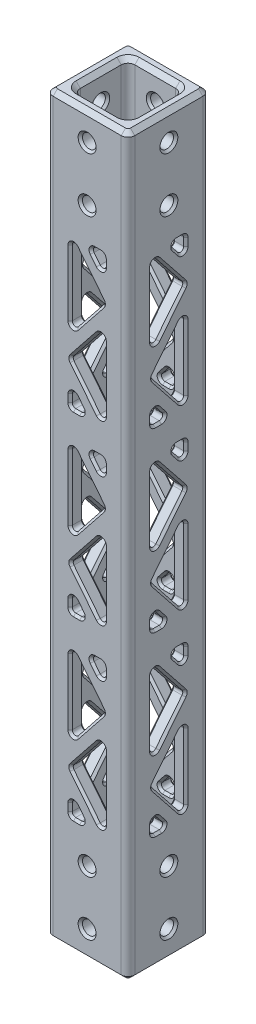
SolidWorks part; units mm, degrees
note: '?' marks a value the reader was unsure of.
ref_plane "Front Plane" through (0, 0, 0) normal (0, 0, 1) x (1, 0, 0)
ref_plane "Top Plane" through (0, 0, 0) normal (0, 1, 0) x (1, 0, 0)
ref_plane "Right Plane" through (0, 0, 0) normal (1, 0, 0) x (0, 0, -1)
sketch "Sketch1" plane through (0, 0, 0) normal (0, 1, 0) x (1, 0, 0)
  line L1 (-9.525, -9.525) -> (9.525, -9.525)
  line L2 (-9.525, -9.525) -> (-9.525, 9.525)
  line L3 (-9.525, 9.525) -> (9.525, 9.525)
  line L4 (9.525, -9.525) -> (9.525, 9.525)
  line L5 (-9.525, -9.525) -> (9.525, 9.525) construction
  line L6 (-9.525, 9.525) -> (9.525, -9.525) construction
  line L7 (-6.35, -6.35) -> (6.35, -6.35)
  line L8 (-6.35, -6.35) -> (-6.35, 6.35)
  line L9 (-6.35, 6.35) -> (6.35, 6.35)
  line L10 (6.35, -6.35) -> (6.35, 6.35)
  line L11 (-6.35, -6.35) -> (6.35, 6.35) construction
  line L12 (-6.35, 6.35) -> (6.35, -6.35) construction
  point P0 (0, 0)
  point P6 (0, 0)
  dimension "D1" = 19.05
  dimension "D2" = 19.05
  dimension "D3" = 12.7
extrude "Boss-Extrude1" add sketch "Sketch1" along normal mid plane 171.45 contours L3 L4 L1 L2
hole_wizard "1/8 (0.125) Diameter Hole1" positions "Sketch8" profile "Sketch9" hole size "1/8" standard "ANSI Inch" end condition through all
sketch "Sketch8" plane through (-9.525, 0, 0) normal (-1, 0, 0) x (0, 0, 1)
  line L4 (-9.525, 85.725) -> (9.525, 85.725) construction
  line L5 (0, 79.375) -> (0, 85.725) construction
  point P0 (0, 79.375)
  point P2 (0, 66.675)
  dimension "D1" = 12.7
  dimension "D2" = 6.35
sketch "Sketch9" plane through (-9.525, 79.375, 0) normal (0, 1, 0) x (0, 0, 1)
  line L0 (0, 0) -> (0, 19.05)
  line L1 (0, 19.05) -> (1.5875, 19.05)
  line L2 (1.5875, 19.05) -> (1.5875, 0)
  line L5 (1.5875, 0) -> (0, 0)
  line L11 (0, -6.35) -> (0, 107.95) construction
  dimension "Thru Hole Dia." = 3.175
  dimension "Thru Hole Depth" = 19.05
hole_wizard "1/8 (0.125) Diameter Hole2" positions "Sketch10" profile "Sketch11" hole size "1/8" standard "ANSI Inch" end condition through all
sketch "Sketch10" plane through (-9.525, 0, 0) normal (-1, 0, 0) x (0, 0, 1)
  line L0 (0, -85.725) -> (0, -79.375) construction
  line L1 (-9.525, -85.725) -> (9.525, -85.725) construction
  point P0 (0, -66.675)
  point P2 (0, -79.375)
  dimension "D1" = 12.7
  dimension "D2" = 6.35
sketch "Sketch11" plane through (-9.525, -66.675, 0) normal (0, 1, 0) x (0, 0, 1)
  line L0 (0, 0) -> (0, 19.05)
  line L1 (0, 19.05) -> (1.5875, 19.05)
  line L2 (1.5875, 19.05) -> (1.5875, 0)
  line L5 (1.5875, 0) -> (0, 0)
  line L11 (0, -6.35) -> (0, 107.95) construction
  dimension "Thru Hole Dia." = 3.175
  dimension "Thru Hole Depth" = 19.05
hole_wizard "1/8 (0.125) Diameter Hole3" positions "Sketch15" profile "Sketch16" hole size "1/8" standard "ANSI Inch" end condition through all
sketch "Sketch15" plane through (0, 0, 9.525) normal (0, 0, 1) x (1, 0, 0)
  line L0 (0, -85.725) -> (0, -79.375) construction
  line L1 (-9.525, -85.725) -> (9.525, -85.725) construction
  line L2 (0, -79.375) -> (0, -66.675) construction
  line L4 (0, 66.675) -> (0, 79.375) construction
  line L5 (0, 79.375) -> (0, 85.725) construction
  line L6 (-9.525, 85.725) -> (9.525, 85.725) construction
  point P0 (0, 79.375)
  point P2 (0, 66.675)
  point P4 (0, -66.675)
  point P6 (0, -79.375)
  dimension "D1" = 6.35
  dimension "D2" = 12.7
sketch "Sketch16" plane through (0, 79.375, 9.525) normal (1, 0, 0) x (0, -1, 0)
  line L0 (0, 0) -> (0, 19.05)
  line L1 (0, 19.05) -> (1.5875, 19.05)
  line L2 (1.5875, 19.05) -> (1.5875, 0)
  line L5 (1.5875, 0) -> (0, 0)
  line L11 (0, -6.35) -> (0, 107.95) construction
  dimension "Thru Hole Dia." = 3.175
  dimension "Thru Hole Depth" = 19.05
sketch "Sketch14" plane through (0, 0, 0) normal (1, 0, 0) x (0, 0, -1)
  line L0 (-3.9688, 58.7375) -> (3.9688, 58.7375) construction
  line L3 (3.9688, 58.7375) -> (3.9688, -58.7375) construction
  line L6 (3.9688, -58.7375) -> (-3.9688, -58.7375) construction
  line L9 (-3.9688, -58.7375) -> (-3.9688, 58.7375) construction
  line L10 (0, 58.7375) -> (0, 65.0875) construction
  line L11 (0, -65.0875) -> (0, -58.7375) construction
  line L12 (-3.9688, 23.8125) -> (3.9688, 23.8125) construction
  line L13 (-3.9688, 17.4625) -> (3.9688, 17.4625) construction
  line L14 (-3.9688, -17.4625) -> (3.9688, -17.4625) construction
  line L15 (-3.9688, -23.8125) -> (3.9688, -23.8125) construction
  line L16 (0, -58.7375) -> (0, -23.8125) construction
  line L17 (0, -23.8125) -> (0, -17.4625) construction
  line L18 (0, -17.4625) -> (0, 17.4625) construction
  line L19 (0, 17.4625) -> (0, 23.8125) construction
  line L20 (0, 23.8125) -> (0, 58.7375) construction
  line L21 (-3.9688, 58.7375) -> (-0.0935, 58.7375)
  line L22 (-0.0935, 58.7375) -> (-3.9688, 53.8821)
  line L23 (-3.9688, 53.8821) -> (-3.9688, 58.7375)
  line L24 (3.9688, 58.7375) -> (-3.9688, 48.7924)
  line L25 (-3.9688, 48.7924) -> (3.9688, 38.8473)
  line L26 (3.9688, 38.8473) -> (3.9688, 58.7375)
  line L27 (-3.9688, 23.8125) -> (3.9688, 33.7576)
  line L28 (3.9688, 33.7576) -> (-3.9688, 43.7027)
  line L29 (-3.9688, 43.7027) -> (-3.9688, 23.8125)
  line L30 (0, 53.765) -> (-2.4815, 55.7455) construction
  line L31 (0, 43.8199) -> (-2.4815, 41.8393) construction
  line L32 (0.0935, 23.8125) -> (3.9688, 23.8125)
  line L33 (3.9688, 23.8125) -> (3.9688, 28.6679)
  line L34 (3.9688, 28.6679) -> (0.0935, 23.8125)
  line L35 (0, 28.785) -> (2.4815, 26.8045) construction
  line L36 (-3.9688, 17.4625) -> (-0.0935, 17.4625)
  line L37 (-0.0935, 17.4625) -> (-3.9688, 12.6071)
  line L38 (-3.9688, 12.6071) -> (-3.9688, 17.4625)
  line L39 (3.9688, 17.4625) -> (-3.9688, 7.5174)
  line L40 (-3.9688, 7.5174) -> (3.9688, -2.4277)
  line L41 (3.9688, -2.4277) -> (3.9688, 17.4625)
  line L42 (0, 12.49) -> (-2.4815, 14.4705) construction
  line L43 (-3.9688, -17.4625) -> (3.9688, -7.5174)
  line L44 (3.9688, -7.5174) -> (-3.9688, 2.4277)
  line L45 (-3.9688, 2.4277) -> (-3.9688, -17.4625)
  line L46 (0, -2.5449) -> (2.4815, -0.5643) construction
  line L47 (0.0935, -17.4625) -> (3.9688, -17.4625)
  line L48 (3.9688, -17.4625) -> (3.9688, -12.6071)
  line L49 (3.9688, -12.6071) -> (0.0935, -17.4625)
  line L50 (2.0311, -15.0348) -> (-0.4504, -13.0542) construction
  line L51 (-3.9688, -23.8125) -> (-0.0935, -23.8125)
  line L52 (-0.0935, -23.8125) -> (-3.9688, -28.6679)
  line L53 (-3.9688, -28.6679) -> (-3.9688, -23.8125)
  line L54 (3.9688, -23.8125) -> (-3.9688, -33.7576)
  line L55 (-3.9688, -33.7576) -> (3.9688, -43.7027)
  line L56 (3.9688, -43.7027) -> (3.9688, -23.8125)
  line L57 (3.9688, -58.7375) -> (0.0935, -58.7375)
  line L58 (0.0935, -58.7375) -> (3.9688, -53.8821)
  line L59 (3.9688, -53.8821) -> (3.9688, -58.7375)
  line L60 (-3.9688, -58.7375) -> (3.9688, -48.7924)
  line L61 (3.9688, -48.7924) -> (-3.9688, -38.8473)
  line L62 (-3.9688, -38.8473) -> (-3.9688, -58.7375)
  line L63 (0, -28.785) -> (-2.4815, -26.8045) construction
  line L64 (0, -38.7301) -> (-2.4815, -40.7107) construction
  line L65 (2.0311, -56.3098) -> (-0.4504, -54.3292) construction
  circle A8 centre (0, 66.675) radius 1.5875 construction
  circle A9 centre (0, -66.675) radius 1.5875 construction
  dimension "D3" = 3.175
  dimension "D2" = 6.35
  dimension "D1" = 7.9375
extrude "Cut-Extrude1" cut sketch "Sketch14" against normal up to next
ref_axis "Axis1" through (0, -87.3125, 0) along (0, 1, 0)?
pattern_circular "CirPattern1" count 4 over 360 about axis through (0, 0, 0) along (0, 1, 0) of "Cut-Extrude1"
fillet "Fillet1" radius 1.5875 8 edges at (9.525, 0, -9.525) (9.525, 0, 9.525) (-9.525, 0, -9.525) (-9.525, 0, 9.525) (6.35, 0, -6.35) (6.35, 0, 6.35) (-6.35, 0, 6.35) (-6.35, 0, -6.35)
fillet "Fillet2" radius 0.7937 71 edges at (-3.9688, -33.7576, -7.9375) (-3.9688, -28.6679, -7.9375) (-0.0935, -23.8125, -7.9375) (-3.9688, -23.8125, -7.9375) (-3.9688, -17.4625, -7.9375) (3.9687, -7.5174, -7.9375) (-3.9688, 2.4277, -7.9375) (-3.9688, 12.6071, -7.9375) (-3.9688, -58.7375, -7.9375) (3.9687, -12.6071, -7.9375) (3.9687, -53.8821, -7.9375) (0.0935, -58.7375, -7.9375) (3.9687, 58.7375, -7.9375) (-3.9688, 53.8821, -7.9375) (-0.0935, 58.7375, -7.9375) (-3.9688, 58.7375, -7.9375) (7.9375, -43.7027, 3.9688) (7.9375, -28.6679, -3.9688) (7.9375, -23.8125, -0.0935) (7.9375, -17.4625, -3.9687) (7.9375, -7.5174, 3.9687) (7.9375, 2.4277, -3.9688) (7.9375, 17.4625, 3.9688) (7.9375, 23.8125, 0.0935) (7.9375, 33.7576, 3.9688) (7.9375, 43.7027, -3.9688) (7.9375, 17.4625, -0.0935) (7.9375, 17.4625, -3.9688) (7.9375, -58.7375, -3.9687) (7.9375, -48.7924, 3.9688) (7.9375, -17.4625, 0.0935) (7.9375, -17.4625, 3.9688) (7.9375, -12.6071, 3.9688) (7.9375, 58.7375, 3.9688) (7.9375, 48.7924, -3.9687) (3.9688, -28.6679, 7.9375) (-3.9687, 28.6679, 7.9375) (-0.0935, 23.8125, 7.9375) (3.9688, 23.8125, 7.9375) (3.9688, 43.7027, 7.9375) (3.9688, 12.6071, 7.9375) (0.0935, 17.4625, 7.9375) (3.9688, 17.4625, 7.9375) (3.9688, -38.8473, 7.9375) (-0.0935, -17.4625, 7.9375) (-3.9687, -17.4625, 7.9375) (-3.9687, 58.7375, 7.9375) (3.9688, 48.7924, 7.9375) (0.0935, 58.7375, 7.9375) (3.9688, 58.7375, 7.9375) (7.9375, 58.7375, -3.9688) (-7.9375, -58.7375, -0.0935) (-7.9375, -58.7375, -3.9688) (-7.9375, -48.7924, -3.9687) (-7.9375, -58.7375, 3.9687) (-7.9375, -43.7027, -3.9688) (-7.9375, -28.6679, 3.9688) (-7.9375, -17.4625, -3.9688) (-7.9375, -17.4625, 3.9687) (-7.9375, 2.4277, 3.9688) (-7.9375, -7.5174, -3.9687) (-7.9375, -2.4277, -3.9688) (-7.9375, 12.6071, 3.9687) (-7.9375, 17.4625, 3.9688) (-7.9375, 28.6679, -3.9688) (-7.9375, 43.7027, 3.9688) (-7.9375, 48.7924, 3.9688) (-7.9375, 38.8473, -3.9688) (-7.9375, 58.7375, -3.9688) (-7.9375, 58.7375, 0.0935) (-7.9375, 58.7375, 3.9688)
chamfer "Chamfer2" distance 1.016 angle 45 32 edges at (5.885, 85.725, -5.885) (0, 85.725, -6.35) (-5.885, 85.725, -5.885) (-6.35, 85.725, 0) (-5.885, 85.725, 5.885) (0, 85.725, 6.35) (5.885, 85.725, 5.885) (6.35, 85.725, 0) (9.06, 85.725, 9.06) (0, 85.725, 9.525) (-9.06, 85.725, 9.06) (-9.525, 85.725, 0) (-9.06, 85.725, -9.06) (0, 85.725, -9.525) (9.06, 85.725, -9.06) (9.525, 85.725, 0) (-5.885, -85.725, -5.885) (0, -85.725, -6.35) (5.885, -85.725, -5.885) (6.35, -85.725, 0) (5.885, -85.725, 5.885) (0, -85.725, 6.35) (-5.885, -85.725, 5.885) (-6.35, -85.725, 0) (-9.06, -85.725, -9.06) (-9.525, -85.725, 0) (-9.06, -85.725, 9.06) (0, -85.725, 9.525) (9.06, -85.725, 9.06) (9.525, -85.725, 0) (9.06, -85.725, -9.06) (0, -85.725, -9.525)
chamfer "Chamfer1" distance 0.508 angle 45 608 edges at (-3.4373, 25.3303, -6.35) (-3.4373, 25.3303, -9.525) (3.7469, 33.7576, -6.35) (3.7469, 33.7576, -9.525) (-3.4373, 42.1849, -6.35) (-3.4373, 42.1849, -9.525) (-3.4373, 14.1249, -6.35) (-3.4373, 14.1249, -9.525) (-1.0274, 17.013, -6.35) (-1.0274, 17.013, -9.525) (-3.7363, 17.23, -6.35) (-3.7363, 17.23, -9.525) (-3.4373, -57.2197, -6.35) (-3.4373, -57.2197, -9.525) (3.7469, -48.7924, -6.35) (3.7469, -48.7924, -9.525) (-3.4373, -40.3651, -6.35) (-3.4373, -40.3651, -9.525) (1.0274, -17.013, -6.35) (1.0274, -17.013, -9.525) (3.7363, -17.23, -6.35) (3.7363, -17.23, -9.525) (3.4373, -14.1249, -6.35) (3.4373, -14.1249, -9.525) (3.4373, -55.3999, -6.35) (3.4373, -55.3999, -9.525) (1.0274, -58.288, -6.35) (1.0274, -58.288, -9.525) (3.7363, -58.505, -6.35) (3.7363, -58.505, -9.525) (3.4373, 57.2197, -6.35) (3.4373, 57.2197, -9.525) (-3.7469, 48.7924, -6.35) (-3.7469, 48.7924, -9.525) (3.4373, 40.3651, -6.35) (3.4373, 40.3651, -9.525) (-3.4373, 55.3999, -6.35) (-3.4373, 55.3999, -9.525) (-1.0274, 58.288, -6.35) (-1.0274, 58.288, -9.525) (-3.7363, 58.505, -6.35) (-3.7363, 58.505, -9.525) (6.35, -25.3303, 3.4373) (9.525, -25.3303, 3.4373) (6.35, -33.7576, -3.7469) (9.525, -33.7576, -3.7469) (6.35, -42.1849, 3.4373) (9.525, -42.1849, 3.4373) (6.35, -27.1501, -3.4373) (9.525, -27.1501, -3.4373) (6.35, -24.262, -1.0274) (9.525, -24.262, -1.0274) (6.35, -24.045, -3.7363) (9.525, -24.045, -3.7363) (6.35, -15.9447, -3.4373) (9.525, -15.9447, -3.4373) (6.35, -7.5174, 3.7469) (9.525, -7.5174, 3.7469) (6.35, 0.9099, -3.4373) (9.525, 0.9099, -3.4373) (6.35, 15.9447, 3.4373) (9.525, 15.9447, 3.4373) (6.35, 7.5174, -3.7469) (9.525, 7.5174, -3.7469) (6.35, -0.9099, 3.4373) (9.525, -0.9099, 3.4373) (6.35, 27.1501, 3.4373) (9.525, 27.1501, 3.4373) (6.35, 24.262, 1.0274) (9.525, 24.262, 1.0274) (6.35, 24.045, 3.7363) (9.525, 24.045, 3.7363) (6.35, 25.3303, -3.4373) (9.525, 25.3303, -3.4373) (6.35, 33.7576, 3.7469) (9.525, 33.7576, 3.7469) (6.35, 42.1849, -3.4373) (9.525, 42.1849, -3.4373) (6.35, 14.1249, -3.4373) (9.525, 14.1249, -3.4373) (6.35, 17.013, -1.0274) (9.525, 17.013, -1.0274) (6.35, 17.23, -3.7363) (9.525, 17.23, -3.7363) (6.35, -57.2197, -3.4373) (9.525, -57.2197, -3.4373) (6.35, -48.7924, 3.7469) (9.525, -48.7924, 3.7469) (6.35, -40.3651, -3.4373) (9.525, -40.3651, -3.4373) (6.35, -17.013, 1.0274) (9.525, -17.013, 1.0274) (6.35, -17.23, 3.7363) (9.525, -17.23, 3.7363) (6.35, -14.1249, 3.4373) (9.525, -14.1249, 3.4373) (6.35, -55.3999, 3.4373) (9.525, -55.3999, 3.4373) (6.35, -58.288, 1.0274) (9.525, -58.288, 1.0274) (6.35, -58.505, 3.7363) (9.525, -58.505, 3.7363) (6.35, 57.2197, 3.4373) (9.525, 57.2197, 3.4373) (6.35, 48.7924, -3.7469) (9.525, 48.7924, -3.7469) (6.35, 40.3651, 3.4373) (9.525, 40.3651, 3.4373) (6.35, 55.3999, -3.4373) (9.525, 55.3999, -3.4373) (6.35, 58.288, -1.0274) (9.525, 58.288, -1.0274) (-3.4373, -25.3303, 6.35) (-3.4373, -25.3303, 9.525) (3.7469, -33.7576, 6.35) (3.7469, -33.7576, 9.525) (-3.4373, -42.1849, 6.35) (-3.4373, -42.1849, 9.525) (3.4373, -27.1501, 6.35) (3.4373, -27.1501, 9.525) (1.0274, -24.262, 6.35) (1.0274, -24.262, 9.525) (3.7363, -24.045, 6.35) (3.7363, -24.045, 9.525) (3.4373, -15.9447, 6.35) (3.4373, -15.9447, 9.525) (-3.7469, -7.5174, 6.35) (-3.7469, -7.5174, 9.525) (3.4373, 0.9099, 6.35) (3.4373, 0.9099, 9.525) (-3.4373, 15.9447, 6.35) (-3.4373, 15.9447, 9.525) (3.7469, 7.5174, 6.35) (3.7469, 7.5174, 9.525) (-3.4373, -0.9099, 6.35) (-3.4373, -0.9099, 9.525) (-3.4373, 27.1501, 6.35) (-3.4373, 27.1501, 9.525) (-1.0274, 24.262, 6.35) (-1.0274, 24.262, 9.525) (-3.7363, 24.045, 6.35) (-3.7363, 24.045, 9.525) (3.4373, 25.3303, 6.35) (3.4373, 25.3303, 9.525) (-3.7469, 33.7576, 6.35) (-3.7469, 33.7576, 9.525) (3.4373, 42.1849, 6.35) (3.4373, 42.1849, 9.525) (3.4373, 14.1249, 6.35) (3.4373, 14.1249, 9.525) (1.0274, 17.013, 6.35) (1.0274, 17.013, 9.525) (3.7363, 17.23, 6.35) (3.7363, 17.23, 9.525) (3.4373, -57.2197, 6.35) (3.4373, -57.2197, 9.525) (-3.7469, -48.7924, 6.35) (-3.7469, -48.7924, 9.525) (3.4373, -40.3651, 6.35) (3.4373, -40.3651, 9.525) (-1.0274, -17.013, 6.35) (-1.0274, -17.013, 9.525) (-3.7363, -17.23, 6.35) (-3.7363, -17.23, 9.525) (-3.4373, -14.1249, 6.35) (-3.4373, -14.1249, 9.525) (-3.4373, -55.3999, 6.35) (-3.4373, -55.3999, 9.525) (-1.0274, -58.288, 6.35) (-1.0274, -58.288, 9.525) (-3.7363, -58.505, 6.35) (-3.7363, -58.505, 9.525) (-3.4373, 57.2197, 6.35) (-3.4373, 57.2197, 9.525) (3.7469, 48.7924, 6.35) (3.7469, 48.7924, 9.525) (-3.4373, 40.3651, 6.35) (-3.4373, 40.3651, 9.525) (3.4373, 55.3999, 6.35) (3.4373, 55.3999, 9.525) (1.0274, 58.288, 6.35) (1.0274, 58.288, 9.525) (3.7363, 58.505, 6.35) (3.7363, 58.505, 9.525) (6.35, 58.505, -3.7363) (9.525, 58.505, -3.7363) (6.35, 66.675, 1.5875) (-6.35, 66.675, -1.5875) (-9.525, 66.675, 1.5875) (9.525, 66.675, 1.5875) (6.35, 79.375, 1.5875) (-6.35, 79.375, -1.5875) (-9.525, 79.375, 1.5875) (9.525, 79.375, 1.5875) (6.35, -79.375, 1.5875) (-6.35, -79.375, -1.5875) (-9.525, -79.375, 1.5875) (9.525, -79.375, 1.5875) (6.35, -66.675, 1.5875) (-6.35, -66.675, -1.5875) (-9.525, -66.675, 1.5875) (9.525, -66.675, 1.5875) (-9.525, -58.7375, -2.4588) (-6.35, -58.7375, -2.4588) (-9.525, -56.5513, -1.8384) (-6.35, -56.5513, -1.8384) (-9.525, -57.0464, -3.9688) (-6.35, -57.0464, -3.9688) (-9.525, -44.4582, -0.5095) (-6.35, -44.4582, -0.5095) (-9.525, -53.1266, -0.5095) (-6.35, -53.1266, -0.5095) (-9.525, -48.7924, 3.9688) (-6.35, -48.7924, 3.9688) (-9.525, -38.0918, 0.5095) (-6.35, -38.0918, 0.5095) (-9.525, -29.4234, 0.5095) (-6.35, -29.4234, 0.5095) (-9.525, -33.7576, -3.9688) (-6.35, -33.7576, -3.9688) (-9.525, -25.9987, 1.8384) (-6.35, -25.9987, 1.8384) (-9.525, -25.5036, 3.9688) (-6.35, -25.5036, 3.9688) (-9.525, -23.8125, 2.4588) (-6.35, -23.8125, 2.4588) (-9.525, -15.7714, -3.9688) (-6.35, -15.7714, -3.9688) (-9.525, -17.4625, -2.4588) (-6.35, -17.4625, -2.4588) (-9.525, -15.2763, -1.8384) (-6.35, -15.2763, -1.8384) (-9.525, -11.8516, -0.5095) (-6.35, -11.8516, -0.5095) (-9.525, -7.5174, 3.9688) (-6.35, -7.5174, 3.9688) (-9.525, -3.1832, -0.5095) (-6.35, -3.1832, -0.5095) (-9.525, 3.1832, 0.5095) (-6.35, 3.1832, 0.5095) (-9.525, 11.8516, 0.5095) (-6.35, 11.8516, 0.5095) (-9.525, 7.5174, -3.9688) (-6.35, 7.5174, -3.9688) (-9.525, 17.4625, 2.4588) (-6.35, 17.4625, 2.4588) (-9.525, 15.2763, 1.8384) (-6.35, 15.2763, 1.8384) (-9.525, 15.7714, 3.9688) (-6.35, 15.7714, 3.9688) (-9.525, 23.8125, -2.4588) (-6.35, 23.8125, -2.4588) (-9.525, 25.9987, -1.8384) (-6.35, 25.9987, -1.8384) (-9.525, 25.5036, -3.9688) (-6.35, 25.5036, -3.9688) (-9.525, 38.0918, -0.5095) (-6.35, 38.0918, -0.5095) (-9.525, 29.4234, -0.5095) (-6.35, 29.4234, -0.5095) (-9.525, 33.7576, 3.9688) (-6.35, 33.7576, 3.9688) (-1.5875, -79.375, 6.35) (-9.525, 44.4582, 0.5095) (1.5875, -79.375, -6.35) (-6.35, 44.4582, 0.5095) (1.5875, -79.375, -9.525) (-9.525, 53.1266, 0.5095) (1.5875, -79.375, 9.525) (-6.35, 53.1266, 0.5095) (-9.525, 48.7924, -3.9688) (-6.35, 48.7924, -3.9688) (-9.525, 58.7375, 2.4588) (-6.35, 58.7375, 2.4588) (-9.525, 56.5513, 1.8384) (-6.35, 56.5513, 1.8384) (-9.525, 57.0464, 3.9688) (-6.35, 57.0464, 3.9688) (-0.5095, -29.4234, -9.525) (-0.5095, -29.4234, -6.35) (3.9687, -33.7576, -9.525) (3.9687, -33.7576, -6.35) (-0.5095, -38.0918, -9.525) (-0.5095, -38.0918, -6.35) (-1.8384, -25.9987, -9.525) (-1.8384, -25.9987, -6.35) (-3.9688, -25.5036, -9.525) (-3.9688, -25.5036, -6.35) (-2.4588, -23.8125, -9.525) (-2.4588, -23.8125, -6.35) (0.5095, -11.8516, -9.525) (0.5095, -11.8516, -6.35) (-3.9688, -7.5174, -9.525) (-3.9688, -7.5174, -6.35) (0.5095, -3.1832, -9.525) (0.5095, -3.1832, -6.35) (-0.5095, 11.8516, -9.525) (-0.5095, 11.8516, -6.35) (3.9687, 7.5174, -9.525) (3.9687, 7.5174, -6.35) (-0.5095, 3.1832, -9.525) (-0.5095, 3.1832, -6.35) (1.8384, 25.9987, -9.525) (1.8384, 25.9987, -6.35) (3.9687, 25.5036, -9.525) (3.9687, 25.5036, -6.35) (2.4588, 23.8125, -9.525) (2.4588, 23.8125, -6.35) (0.5095, 29.4234, -9.525) (0.5095, 29.4234, -6.35) (-3.9688, 33.7576, -9.525) (-3.9688, 33.7576, -6.35) (0.5095, 38.0918, -9.525) (0.5095, 38.0918, -6.35) (-1.8384, 15.2763, -9.525) (-1.8384, 15.2763, -6.35) (-3.9688, 15.7714, -9.525) (-3.9688, 15.7714, -6.35) (-2.4588, 17.4625, -9.525) (-2.4588, 17.4625, -6.35) (0.5095, -53.1266, -9.525) (0.5095, -53.1266, -6.35) (-3.9688, -48.7924, -9.525) (-3.9688, -48.7924, -6.35) (0.5095, -44.4582, -9.525) (0.5095, -44.4582, -6.35) (2.4588, -17.4625, -9.525) (2.4588, -17.4625, -6.35) (1.8384, -15.2763, -9.525) (1.8384, -15.2763, -6.35) (3.9687, -15.7714, -9.525) (3.9687, -15.7714, -6.35) (1.8384, -56.5513, -9.525) (1.8384, -56.5513, -6.35) (3.9687, -57.0464, -9.525) (3.9687, -57.0464, -6.35) (2.4588, -58.7375, -9.525) (2.4588, -58.7375, -6.35) (-0.5095, 53.1266, -9.525) (-0.5095, 53.1266, -6.35) (3.9687, 48.7924, -9.525) (3.9687, 48.7924, -6.35) (-0.5095, 44.4582, -9.525) (-0.5095, 44.4582, -6.35) (1.5875, -66.675, -6.35) (-1.8384, 56.5513, -9.525) (-1.8384, 56.5513, -6.35) (-1.5875, -66.675, 6.35) (1.5875, -66.675, 9.525) (-3.9688, 57.0464, -9.525) (1.5875, -66.675, -9.525) (-3.9688, 57.0464, -6.35) (-2.4588, 58.7375, -9.525) (-2.4588, 58.7375, -6.35) (9.525, -29.4234, -0.5095) (6.35, -29.4234, -0.5095) (9.525, -33.7576, 3.9688) (6.35, -33.7576, 3.9688) (9.525, -38.0918, -0.5095) (6.35, -38.0918, -0.5095) (9.525, -25.9987, -1.8384) (6.35, -25.9987, -1.8384) (9.525, -25.5036, -3.9688) (6.35, -25.5036, -3.9688) (9.525, -23.8125, -2.4588) (6.35, -23.8125, -2.4588) (9.525, -11.8516, 0.5095) (6.35, -11.8516, 0.5095) (9.525, -7.5174, -3.9688) (6.35, -7.5174, -3.9688) (9.525, -3.1832, 0.5095) (6.35, -3.1832, 0.5095) (9.525, 11.8516, -0.5095) (6.35, 11.8516, -0.5095) (9.525, 7.5174, 3.9688) (6.35, 7.5174, 3.9688) (9.525, 3.1832, -0.5095) (6.35, 3.1832, -0.5095) (9.525, 25.9987, 1.8384) (6.35, 25.9987, 1.8384) (9.525, 25.5036, 3.9688) (6.35, 25.5036, 3.9688) (9.525, 23.8125, 2.4588) (6.35, 23.8125, 2.4588) (9.525, 29.4234, 0.5095) (6.35, 29.4234, 0.5095) (9.525, 33.7576, -3.9688) (6.35, 33.7576, -3.9688) (9.525, 38.0918, 0.5095) (6.35, 38.0918, 0.5095) (9.525, 15.2763, -1.8384) (6.35, 15.2763, -1.8384) (9.525, 15.7714, -3.9688) (6.35, 15.7714, -3.9688) (9.525, 17.4625, -2.4588) (6.35, 17.4625, -2.4588) (9.525, -53.1266, 0.5095) (6.35, -53.1266, 0.5095) (9.525, -48.7924, -3.9688) (6.35, -48.7924, -3.9688) (9.525, -44.4582, 0.5095) (6.35, -44.4582, 0.5095) (9.525, -17.4625, 2.4588) (6.35, -17.4625, 2.4588) (9.525, -15.2763, 1.8384) (6.35, -15.2763, 1.8384) (9.525, -15.7714, 3.9688) (6.35, -15.7714, 3.9688) (9.525, -56.5513, 1.8384) (6.35, -56.5513, 1.8384) (9.525, -57.0464, 3.9688) (6.35, -57.0464, 3.9688) (9.525, -58.7375, 2.4588) (6.35, -58.7375, 2.4588) (9.525, 53.1266, -0.5095) (6.35, 53.1266, -0.5095) (9.525, 48.7924, 3.9688) (6.35, 48.7924, 3.9688) (9.525, 44.4582, -0.5095) (6.35, 44.4582, -0.5095) (9.525, 56.5513, -1.8384) (6.35, 56.5513, -1.8384) (9.525, 57.0464, -3.9688) (6.35, 57.0464, -3.9688) (9.525, 58.7375, -2.4588) (6.35, 58.7375, -2.4588) (-1.5875, 66.675, 6.35) (0.5095, -29.4234, 9.525) (0.5095, -29.4234, 6.35) (1.5875, 66.675, -6.35) (1.5875, 66.675, -9.525) (-3.9687, -33.7576, 9.525) (-3.9687, -33.7576, 6.35) (1.5875, 66.675, 9.525) (0.5095, -38.0918, 9.525) (0.5095, -38.0918, 6.35) (1.8384, -25.9987, 9.525) (1.8384, -25.9987, 6.35) (3.9688, -25.5036, 9.525) (3.9688, -25.5036, 6.35) (2.4588, -23.8125, 9.525) (2.4588, -23.8125, 6.35) (-0.5095, -11.8516, 9.525) (-0.5095, -11.8516, 6.35) (3.9688, -7.5174, 9.525) (3.9688, -7.5174, 6.35) (-0.5095, -3.1832, 9.525) (-0.5095, -3.1832, 6.35) (0.5095, 11.8516, 9.525) (0.5095, 11.8516, 6.35) (-3.9687, 7.5174, 9.525) (-3.9687, 7.5174, 6.35) (0.5095, 3.1832, 9.525) (0.5095, 3.1832, 6.35) (-1.8384, 25.9987, 9.525) (-1.8384, 25.9987, 6.35) (-3.9687, 25.5036, 9.525) (-3.9687, 25.5036, 6.35) (-2.4588, 23.8125, 9.525) (-2.4588, 23.8125, 6.35) (-0.5095, 29.4234, 9.525) (-0.5095, 29.4234, 6.35) (3.9688, 33.7576, 9.525) (3.9688, 33.7576, 6.35) (-0.5095, 38.0918, 9.525) (-0.5095, 38.0918, 6.35) (1.8384, 15.2763, 9.525) (1.8384, 15.2763, 6.35) (3.9688, 15.7714, 9.525) (3.9688, 15.7714, 6.35) (2.4588, 17.4625, 9.525) (2.4588, 17.4625, 6.35) (-0.5095, -53.1266, 9.525) (-0.5095, -53.1266, 6.35) (3.9688, -48.7924, 9.525) (3.9688, -48.7924, 6.35) (-0.5095, -44.4582, 9.525) (-0.5095, -44.4582, 6.35) (-2.4588, -17.4625, 9.525) (-2.4588, -17.4625, 6.35) (-1.8384, -15.2763, 9.525) (-1.8384, -15.2763, 6.35) (-3.9687, -15.7714, 9.525) (-3.9687, -15.7714, 6.35) (-1.8384, -56.5513, 9.525) (-1.8384, -56.5513, 6.35) (-3.9687, -57.0464, 9.525) (-3.9687, -57.0464, 6.35) (-2.4588, -58.7375, 9.525) (-2.4588, -58.7375, 6.35) (0.5095, 53.1266, 9.525) (0.5095, 53.1266, 6.35) (-3.9687, 48.7924, 9.525) (-3.9687, 48.7924, 6.35) (0.5095, 44.4582, 9.525) (0.5095, 44.4582, 6.35) (1.8384, 56.5513, 9.525) (1.8384, 56.5513, 6.35) (3.9688, 57.0464, 9.525) (3.9688, 57.0464, 6.35) (2.4588, 58.7375, 9.525) (2.4588, 58.7375, 6.35) (-6.35, -58.288, -1.0274) (-9.525, -58.288, -1.0274) (-6.35, -58.505, -3.7363) (-9.525, -58.505, -3.7363) (-6.35, -55.3999, -3.4373) (-9.525, -55.3999, -3.4373) (-6.35, -48.7924, -3.7469) (-9.525, -48.7924, -3.7469) (-6.35, -57.2197, 3.4373) (-9.525, -57.2197, 3.4373) (-6.35, -40.3651, 3.4373) (-9.525, -40.3651, 3.4373) (-6.35, -33.7576, 3.7469) (-9.525, -33.7576, 3.7469) (-6.35, -42.1849, -3.4373) (-9.525, -42.1849, -3.4373) (-6.35, -25.3303, -3.4373) (-1.5875, 79.375, 6.35) (-9.525, -25.3303, -3.4373) (-6.35, -27.1501, 3.4373) (-9.525, -27.1501, 3.4373) (1.5875, 79.375, -6.35) (-6.35, -24.045, 3.7363) (-9.525, -24.045, 3.7363) (1.5875, 79.375, -9.525) (-6.35, -24.262, 1.0274) (-9.525, -24.262, 1.0274) (-6.35, -17.23, -3.7363) (1.5875, 79.375, 9.525) (-9.525, -17.23, -3.7363) (-6.35, -17.013, -1.0274) (-9.525, -17.013, -1.0274) (-6.35, -14.1249, -3.4373) (-9.525, -14.1249, -3.4373) (-6.35, -15.9447, 3.4373) (-9.525, -15.9447, 3.4373) (-6.35, 0.9099, 3.4373) (-9.525, 0.9099, 3.4373) (-6.35, -7.5174, -3.7469) (-9.525, -7.5174, -3.7469) (-6.35, 7.5174, 3.7469) (-9.525, 7.5174, 3.7469) (-6.35, -0.9099, -3.4373) (-9.525, -0.9099, -3.4373) (-6.35, 15.9447, -3.4373) (-9.525, 15.9447, -3.4373) (-6.35, 17.013, 1.0274) (-9.525, 17.013, 1.0274) (-6.35, 14.1249, 3.4373) (-9.525, 14.1249, 3.4373) (-6.35, 17.23, 3.7363) (-9.525, 17.23, 3.7363) (-6.35, 24.262, -1.0274) (-9.525, 24.262, -1.0274) (-6.35, 24.045, -3.7363) (-9.525, 24.045, -3.7363) (-6.35, 27.1501, -3.4373) (-9.525, 27.1501, -3.4373) (-6.35, 33.7576, -3.7469) (-9.525, 33.7576, -3.7469) (-6.35, 25.3303, 3.4373) (-9.525, 25.3303, 3.4373) (-6.35, 42.1849, 3.4373) (-9.525, 42.1849, 3.4373) (-6.35, 48.7924, 3.7469) (-9.525, 48.7924, 3.7469) (-6.35, 40.3651, -3.4373) (-9.525, 40.3651, -3.4373) (-6.35, 57.2197, -3.4373) (-9.525, 57.2197, -3.4373) (-6.35, 58.288, 1.0274) (-9.525, 58.288, 1.0274) (-6.35, 55.3999, 3.4373) (-9.525, 55.3999, 3.4373) (-6.35, 58.505, 3.7363) (-9.525, 58.505, 3.7363) (3.4373, -25.3303, -6.35) (3.4373, -25.3303, -9.525) (-3.7469, -33.7576, -6.35) (-3.7469, -33.7576, -9.525) (3.4373, -42.1849, -6.35) (3.4373, -42.1849, -9.525) (-3.4373, -27.1501, -6.35) (-3.4373, -27.1501, -9.525) (-1.0274, -24.262, -6.35) (-1.0274, -24.262, -9.525) (-3.7363, -24.045, -6.35) (-3.7363, -24.045, -9.525) (-3.4373, -15.9447, -6.35) (-3.4373, -15.9447, -9.525) (3.7469, -7.5174, -6.35) (3.7469, -7.5174, -9.525) (-3.4373, 0.9099, -6.35) (-3.4373, 0.9099, -9.525) (3.4373, 15.9447, -6.35) (3.4373, 15.9447, -9.525) (-3.7469, 7.5174, -6.35) (-3.7469, 7.5174, -9.525) (3.4373, -0.9099, -6.35) (3.4373, -0.9099, -9.525) (3.4373, 27.1501, -6.35) (3.4373, 27.1501, -9.525) (1.0274, 24.262, -6.35) (1.0274, 24.262, -9.525) (3.7363, 24.045, -6.35) (3.7363, 24.045, -9.525)
equation "\"D2@Sketch1\"=\"D1@Sketch1\""
